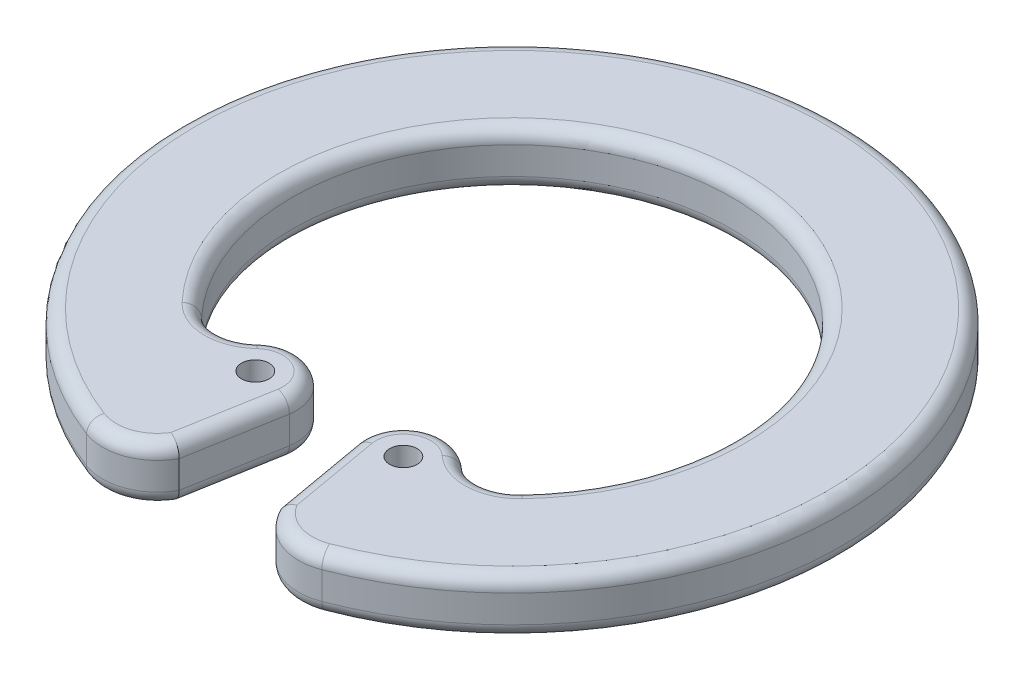
SolidWorks part; units mm, degrees
ref_plane "Front Plane" through (0, 0, 0) normal (0, 0, 1) x (1, 0, 0)
ref_plane "Top Plane" through (0, 0, 0) normal (0, 1, 0) x (1, 0, 0)
ref_plane "Right Plane" through (0, 0, 0) normal (1, 0, 0) x (0, 0, -1)
sketch "Sketch1" plane through (0, 0, 0) normal (0, 1, 0) x (1, 0, 0)
  circle A0 centre (0, 0) radius 8
  circle A1 centre (0, 0) radius 12
  dimension "D1" = 16
  dimension "D2" = 4
extrude "Boss-Extrude1" add sketch "Sketch1" along normal blind 2
sketch "Sketch2" plane through (0, 2, 0) normal (0, 1, 0) x (1, 0, 0)
  line L0 (0, 0) -> (0, -12) construction
  line L1 (-3.5702, -9.341) -> (-2.6962, -6.6535) construction
  line L3 (-1.8167, -10.3029) -> (-1.2155, -6.8937)
  line L4 (3.5702, -9.341) -> (2.6962, -6.6535) construction
  line L5 (1.8167, -10.3029) -> (1.2155, -6.8937)
  circle A0 centre (0, 0) radius 12 construction
  arc A1 (-4.2842, -11.2092) -> (-1.8167, -10.3029) centre (-3.5702, -9.341) ccw
  arc A2 (-1.2155, -6.8937) -> (-3.7157, -5.5532) centre (-2.6962, -6.6535) ccw
  arc A3 (-3.7157, -5.5532) -> (-5.8279, -5.4805) centre (-4.7352, -4.4529) cw
  circle A4 centre (0, 0) radius 8 construction
  arc A5 (3.7157, -5.5532) -> (5.8279, -5.4805) centre (4.7352, -4.4529) ccw
  arc A6 (1.2155, -6.8937) -> (3.7157, -5.5532) centre (2.6962, -6.6535) cw
  arc A7 (4.2842, -11.2092) -> (1.8167, -10.3029) centre (3.5702, -9.341) cw
  arc A8 (4.2842, -11.2092) -> (-4.2842, -11.2092) centre (0, 0) ccw
  arc A9 (5.8279, -5.4805) -> (-5.8279, -5.4805) centre (0, 0) ccw
  point P8 (-3.7609, -7.2526)
  point P13 (2.0838, -11.8177)
  point P27 (3.7609, -7.2526)
  dimension "D2" = 1.5
  dimension "D3" = 1.5
  dimension "D4" = 2
  dimension "D1" = 10
  dimension "D5" = 5
extrude "Cut-Extrude1" cut sketch "Sketch2" against normal through all flip side to cut
extrude "Boss-Extrude2" add sketch "Sketch2<2>" against normal blind 2
sketch "Sketch2<2>" plane through (0, 2, 0) normal (0, 1, 0) x (1, 0, 0) same geometry as "Sketch2"
sketch "Sketch3" plane through (0, 2, 0) normal (0, 1, 0) x (1, 0, 0)
  circle A0 centre (-2.6962, -6.6535) radius 0.5
  circle A1 centre (2.6962, -6.6535) radius 0.5
  dimension "D1" = 1
  dimension "D2" = 1
extrude "Cut-Extrude2" cut sketch "Sketch3" against normal through all
fillet "Fillet2" radius 0.5 20 edges at (1.5161, 2, 8.5983) (1.9874, 2, 5.3315) (4.7868, 2, 5.952) (-1.5161, 2, 8.5983) (-1.9874, 2, 5.3315) (-4.7868, 2, 5.952) (1.5161, 0, 8.5983) (1.9874, 0, 5.3315) (4.7868, 0, 5.952) (-1.5161, 0, 8.5983) (-1.9874, 0, 5.3315) (-4.7868, 0, 5.952) (2.8806, 2, 11.2184) (-2.8806, 2, 11.2184) (2.8806, 0, 11.2184) (-2.8806, 0, 11.2184) (0, 2, -8) (0, 0, -8) (0, 2, -12) (0, 0, -12)
